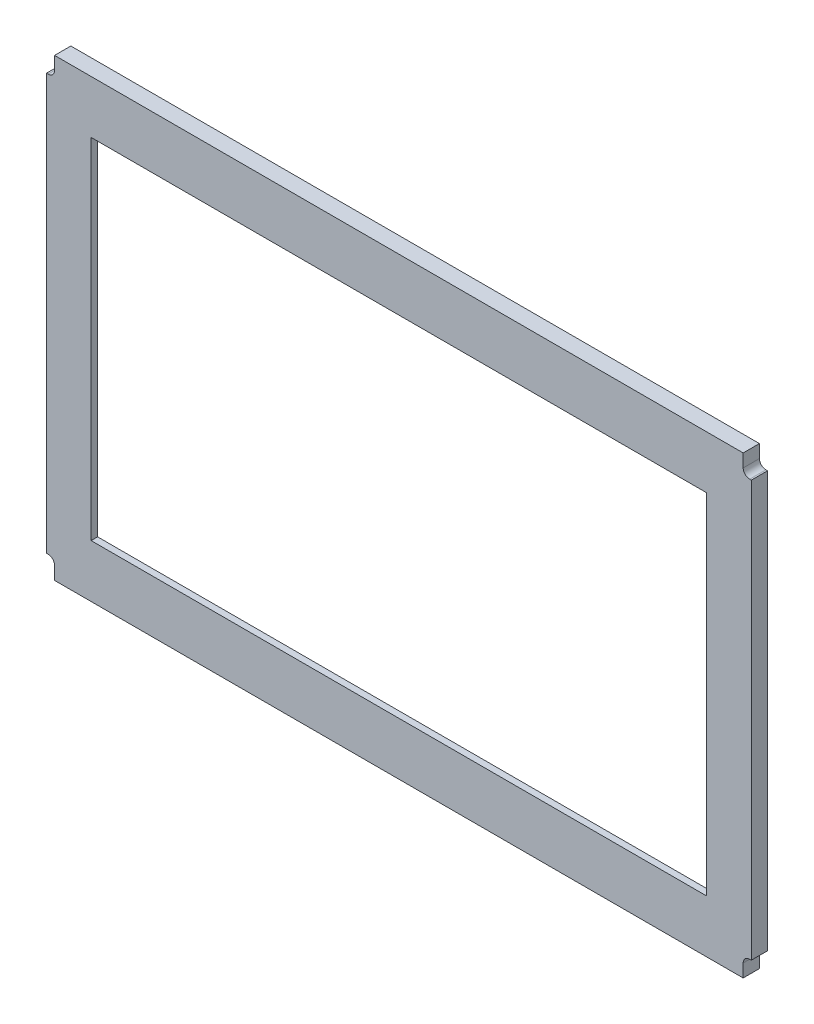
SolidWorks part; units mm, degrees
ref_plane "Front Plane" through (0, 0, 0) normal (0, 0, 1) x (1, 0, 0)
ref_plane "Top Plane" through (0, 0, 0) normal (0, 1, 0) x (1, 0, 0)
ref_plane "Right Plane" through (0, 0, 0) normal (1, 0, 0) x (0, 0, -1)
sketch "Sketch1" plane through (0, 0, 0) normal (0, 0, 1) x (1, 0, 0)
  line L1 (336.55, 222.25) -> (-336.55, 222.25)
  line L2 (336.55, 222.25) -> (336.55, -222.25)
  line L3 (336.55, -222.25) -> (-336.55, -222.25)
  line L4 (-336.55, 222.25) -> (-336.55, -222.25)
  line L5 (336.55, 222.25) -> (-336.55, -222.25) construction
  line L6 (336.55, -222.25) -> (-336.55, 222.25) construction
  point P0 (0, 0)
  dimension "D1" = 444.5
  dimension "D2" = 673.1
extrude "Boss-Extrude1" add sketch "Sketch1" along normal mid plane 15.875
sketch "Sketch2" plane through (0, 0, 7.9375) normal (0, 0, 1) x (1, 0, 0)
  line L0 (0, 0) -> (0, -222.25) construction
  line L1 (300.8312, 170.6562) -> (-300.8313, 170.6562)
  line L2 (300.8312, 170.6562) -> (300.8312, -170.6562)
  line L3 (300.8312, -170.6562) -> (-300.8313, -170.6562)
  line L4 (-300.8313, 170.6562) -> (-300.8313, -170.6562)
  line L5 (300.8312, 170.6562) -> (-300.8313, -170.6562) construction
  line L6 (300.8312, -170.6562) -> (-300.8313, 170.6562) construction
  line L7 (-336.55, -222.25) -> (336.55, -222.25) construction
  point P0 (0, 0)
  dimension "D1" = 341.3125
  dimension "D2" = 601.6625
extrude "Cut-Extrude1" cut sketch "Sketch2" against normal through all both and the other way through all
sketch "Sketch4" plane through (0, 0, 7.9375) normal (0, 0, 1) x (1, 0, 0)
  line L0 (-336.55, 222.25) -> (-336.55, -222.25) construction
  line L1 (-336.55, 203.2) -> (-344.4875, 203.2)
  line L2 (-336.55, 203.2) -> (-336.55, -203.2)
  line L3 (-336.55, -203.2) -> (-344.4875, -203.2)
  line L4 (-344.4875, 203.2) -> (-344.4875, -203.2)
  line L5 (336.55, -222.25) -> (336.55, 222.25) construction
  line L6 (336.55, 203.2) -> (344.4875, 203.2)
  line L7 (336.55, 203.2) -> (336.55, -203.2)
  line L8 (336.55, -203.2) -> (344.4875, -203.2)
  line L9 (344.4875, 203.2) -> (344.4875, -203.2)
  line L10 (336.55, 222.25) -> (-336.55, 222.25) construction
  line L15 (0, 0) -> (0, 230.1875) construction
  line L16 (-336.55, -222.25) -> (336.55, -222.25) construction
  dimension "D1" = 19.05
  dimension "D2" = 19.05
  dimension "D3" = 7.9375
  dimension "D4" = 688.975
extrude "Boss-Extrude2" add sketch "Sketch4" against normal up to surface (15.875 mm away) up to face at (0, 0, -7.9375)
fillet "Fillet1" radius 6.35 4 edges at (336.55, 203.2, 0) (336.55, -203.2, 0) (-336.55, -203.2, 0) (-336.55, 203.2, 0)
sketch "Sketch6" plane through (336.55, 0, 0) normal (1, 0, 0) x (0, 0, -1)
  line L0 (-7.9375, -222.25) -> (7.9375, -215.6744)
  line L2 (7.9375, -215.6744) -> (7.9375, -222.25)
  line L3 (7.9375, -222.25) -> (-7.9375, -222.25)
  dimension "D1" = 22.5
extrude "Cut-Extrude4" [suppressed] cut sketch "Sketch6" against normal through all both and the other way through all
sketch "Sketch7" plane through (0, 0, -7.9375) normal (0, 0, -1) x (-1, 0, 0)
  line L0 (0, 187.325) -> (0, -187.325) construction
  line L1 (-314.325, 0) -> (314.325, 0) construction
  line L2 (300.8313, -170.6562) -> (-300.8312, -170.6562) construction
  line L3 (-300.8312, 170.6562) -> (300.8313, 170.6562) construction
  line L15 (-307.975, -187.325) -> (307.975, -187.325)
  line L16 (314.325, -180.975) -> (314.325, 180.975)
  line L17 (307.975, 187.325) -> (-307.975, 187.325)
  line L18 (-314.325, 180.975) -> (-314.325, -180.975)
  arc A0 (314.325, 180.975) -> (307.975, 187.325) centre (307.975, 180.975) ccw
  arc A1 (307.975, -187.325) -> (314.325, -180.975) centre (307.975, -180.975) ccw
  arc A2 (-307.975, -187.325) -> (-314.325, -180.975) centre (-307.975, -180.975) cw
  arc A3 (-307.975, 187.325) -> (-314.325, 180.975) centre (-307.975, 180.975) ccw
  dimension "D2" = 6.35
  dimension "D1" = 628.65
  dimension "D3" = 374.65
  dimension "D4" = 16.6688
  dimension "D5" = 16.6687
extrude "Cut-Extrude5" cut sketch "Sketch7" against normal blind 9.525
sketch "Sketch8" [suppressed] plane through (0, 0, 7.9375) normal (0, 0, 1) x (1, 0, 0)
  line L0 (300.8312, -170.6562) -> (-300.8313, -170.6562) construction
  line L1 (300.8312, 170.6562) -> (-300.8313, 170.6562)
  line L2 (300.8312, 170.6562) -> (300.8312, -170.6562)
  line L3 (300.8312, -170.6562) -> (-300.8313, -170.6562)
  line L4 (-300.8313, 170.6562) -> (-300.8313, -170.6562)
  line L5 (-300.8313, 170.6562) -> (300.8312, 170.6562) construction
  line L6 (300.8312, 170.6562) -> (300.8312, -170.6562) construction
  line L8 (284.9562, 154.7812) -> (-284.9563, 154.7812)
  line L9 (284.9562, 154.7812) -> (284.9562, -154.7812)
  line L10 (284.9562, -154.7812) -> (-284.9563, -154.7812)
  line L11 (-284.9563, 154.7812) -> (-284.9563, -154.7812)
  point P0 (0, 0)
  point P8 (0, 3.81)
  point P15 (0, 170.6562)
  dimension "D1" = 15.875
  dimension "D2" = 15.875
  dimension "D3" = 15.875
  dimension "D4" = 15.875
extrude "Boss-Extrude3" [suppressed] add sketch "Sketch8" against normal blind 2.54
sketch "Sketch9" [suppressed] plane through (0, 0, 7.9375) normal (0, 0, 1) x (1, 0, 0)
  line L8 (-319.8813, -184.15) -> (319.8812, -184.15)
  line L9 (319.8812, -184.15) -> (319.8812, 195.2625)
  line L10 (319.8812, 195.2625) -> (-319.8813, 195.2625)
  line L11 (-319.8813, 195.2625) -> (-319.8813, -184.15)
  line L12 (-319.8813, -184.15) -> (319.8812, -184.15)
  line L13 (319.8812, -184.15) -> (319.8812, 195.2625)
  line L14 (319.8812, 195.2625) -> (-319.8813, 195.2625)
  line L15 (-319.8813, 195.2625) -> (-319.8813, -184.15)
  dimension "D1" = 19.05
sketch "Sketch10" [suppressed] plane through (0, 0, -7.9375) normal (0, 0, -1) x (-1, 0, 0)
  line L0 (-300.8312, 176.2125) -> (300.8313, 176.2125) construction
  line L1 (300.8313, 176.2125) -> (300.8313, -165.1) construction
  line L2 (-300.8312, -165.1) -> (-300.8312, 176.2125) construction
  line L3 (300.8313, -165.1) -> (-300.8312, -165.1) construction
  line L4 (-300.8312, 176.2125) -> (300.8313, 176.2125)
  line L5 (300.8313, 176.2125) -> (300.8313, -165.1)
  line L6 (-300.8312, -165.1) -> (-300.8312, 176.2125)
  line L7 (300.8313, -165.1) -> (-300.8312, -165.1)
loft "Cut-Loft1" [suppressed] cut profiles "Sketch9", "Sketch10"
